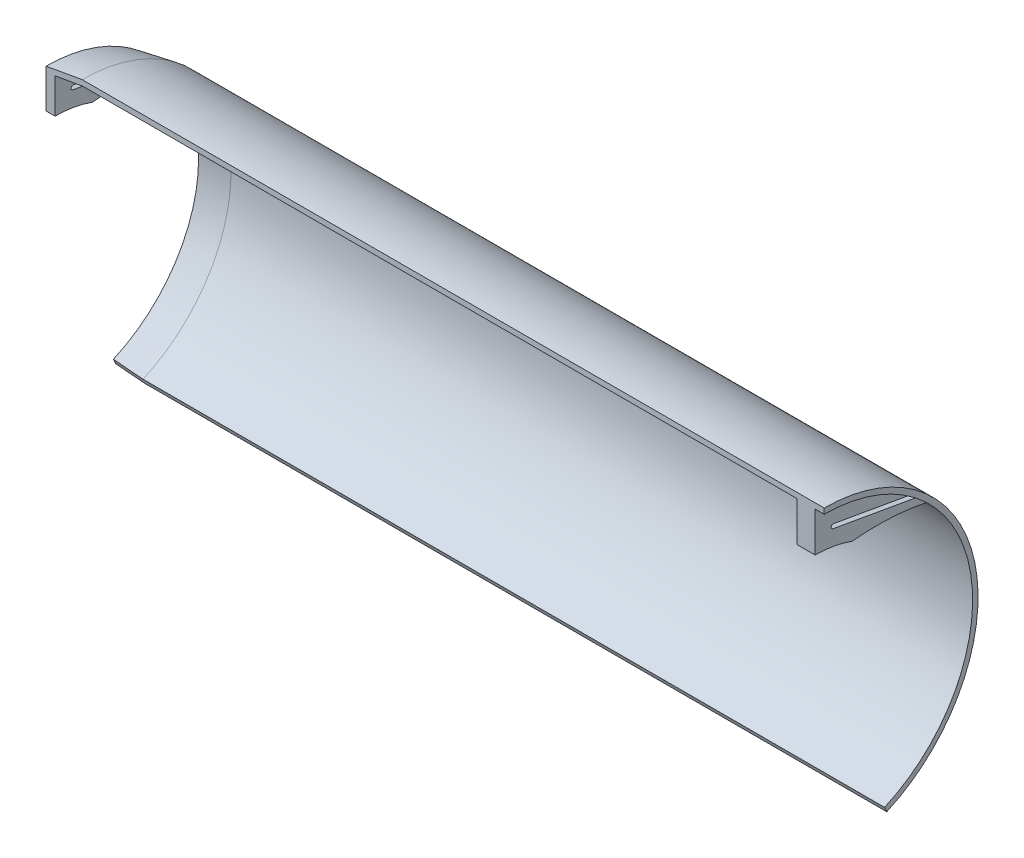
SolidWorks part; units mm, degrees
ref_plane "Front Plane" through (0, 0, 0) normal (0, 0, 1) x (1, 0, 0)
ref_plane "Top Plane" through (0, 0, 0) normal (0, 1, 0) x (1, 0, 0)
ref_plane "Right Plane" through (0, 0, 0) normal (1, 0, 0) x (0, 0, -1)
curve "Curve1"
  spline degree 3 poles (0, 0, 0) (-0.0123, 3.8916, 0) (-0.0274, 8.685, 0) (0.3616, 14.0857, 0) (0.5761, 16.0905, 0) (0.7825, 17.6048, 0) (0.9862, 18.8543, 0) (1.1887, 19.9315, 0) (1.3904, 20.8857, 0) (1.5917, 21.7465, 0) (1.7927, 22.5337, 0) (1.9935, 23.2611, 0) (2.1942, 23.9386, 0) (2.3947, 24.5739, 0) (2.5952, 25.1728, 0) (2.7956, 25.7401, 0) (2.9959, 26.2796, 0) (3.1962, 26.7943, 0) (3.3965, 27.2868, 0) (3.5967, 27.7594, 0) (3.7969, 28.2139, 0) (3.9971, 28.6519, 0) (4.1973, 29.0748, 0) (4.3974, 29.4838, 0) (4.5976, 29.8799, 0) (4.7977, 30.2641, 0) (4.9978, 30.6373, 0) (5.1979, 31.0001, 0) (5.398, 31.3533, 0) (5.5981, 31.6974, 0) (5.7982, 32.033, 0) (5.9983, 32.3606, 0) (6.1984, 32.6807, 0) (6.3985, 32.9935, 0) (6.5985, 33.2996, 0) (6.7986, 33.5993, 0) (6.9986, 33.8929, 0) (7.1987, 34.1806, 0) (7.3987, 34.4628, 0) (7.5988, 34.7397, 0) (7.7988, 35.0115, 0) (7.9989, 35.2785, 0) (8.1989, 35.5408, 0) (8.399, 35.7988, 0) (8.599, 36.0524, 0) (8.799, 36.3019, 0) (8.9991, 36.5476, 0) (9.1991, 36.7894, 0) (9.3991, 37.0275, 0) (9.5992, 37.2622, 0) (9.7992, 37.4934, 0) (9.9992, 37.7214, 0) (10.1992, 37.9461, 0) (10.3993, 38.1679, 0) (10.5993, 38.3866, 0) (10.7993, 38.6025, 0) (10.9993, 38.8156, 0) (11.1993, 39.026, 0) (11.3994, 39.2338, 0) (11.5994, 39.4391, 0) (11.7994, 39.6419, 0) (11.9994, 39.8422, 0) (12.1994, 40.0403, 0) (12.3995, 40.2361, 0) (12.5995, 40.4297, 0) (12.7995, 40.6212, 0) (12.9995, 40.8106, 0) (13.1995, 40.998, 0) (13.3995, 41.1834, 0) (13.5995, 41.3668, 0) (13.7995, 41.5484, 0) (13.9996, 41.7281, 0) (14.1996, 41.9061, 0) (14.3996, 42.0823, 0) (14.5996, 42.2568, 0) (14.7996, 42.4296, 0) (14.9996, 42.6008, 0) (15.1996, 42.7705, 0) (15.3996, 42.9385, 0) (15.5996, 43.1051, 0) (15.7996, 43.2701, 0) (15.9997, 43.4337, 0) (16.1997, 43.5959, 0) (16.3997, 43.7567, 0) (16.5997, 43.9161, 0) (16.7997, 44.0742, 0) (16.9997, 44.2309, 0) (17.1997, 44.3864, 0) (17.3997, 44.5406, 0) (17.5997, 44.6936, 0) (17.7997, 44.8453, 0) (17.9997, 44.9959, 0) (18.1997, 45.1453, 0) (18.3997, 45.2936, 0) (18.5997, 45.4407, 0) (18.7997, 45.5868, 0) (18.9997, 45.7317, 0) (19.1998, 45.8756, 0) (19.3998, 46.0185, 0) (19.5998, 46.1603, 0) (19.7998, 46.3011, 0) (19.9998, 46.4409, 0) (20.1998, 46.5797, 0) (20.3998, 46.7176, 0) (20.5998, 46.8546, 0) (20.7998, 46.9906, 0) (20.9998, 47.1257, 0) (21.1998, 47.2599, 0) (21.3998, 47.3932, 0) (21.5998, 47.5256, 0) (21.7998, 47.6572, 0) (21.9998, 47.788, 0) (22.1998, 47.9179, 0) (22.3998, 48.047, 0) (22.5998, 48.1753, 0) (22.7998, 48.3028, 0) (22.9998, 48.4295, 0) (23.1998, 48.5555, 0) (23.3998, 48.6807, 0) (23.5998, 48.8051, 0) (23.7998, 48.9288, 0) (23.9998, 49.0518, 0) (24.1998, 49.1741, 0) (24.3998, 49.2957, 0) (24.5998, 49.4165, 0) (24.7999, 49.5367, 0) (24.9999, 49.6562, 0) (25.1999, 49.7751, 0) (25.3999, 49.8933, 0) (25.5999, 50.0108, 0) (25.7999, 50.1277, 0) (25.9999, 50.2439, 0) (26.1999, 50.3596, 0) (26.3999, 50.4746, 0) (26.5999, 50.589, 0) (26.7999, 50.7028, 0) (26.9999, 50.8161, 0) (27.1999, 50.9287, 0) (27.3999, 51.0407, 0) (27.5999, 51.1522, 0) (27.7999, 51.2631, 0) (27.9999, 51.3735, 0) (28.1999, 51.4833, 0) (28.3999, 51.5926, 0) (28.5999, 51.7013, 0) (28.7999, 51.8095, 0) (28.9999, 51.9172, 0) (29.1999, 52.0243, 0) (29.3999, 52.131, 0) (29.5999, 52.2371, 0) (29.7999, 52.3428, 0) (29.9999, 52.4479, 0) (30.1999, 52.5526, 0) (30.3999, 52.6567, 0) (30.5999, 52.7604, 0) (30.7999, 52.8636, 0) (30.9999, 52.9664, 0) (31.1999, 53.0687, 0) (31.3999, 53.1705, 0) (31.5999, 53.2719, 0) (31.7999, 53.3728, 0) (31.9999, 53.4733, 0) (32.1999, 53.5733, 0) (32.3999, 53.6729, 0) (32.5999, 53.7721, 0) (32.7999, 53.8709, 0) (32.9999, 53.9692, 0) (33.1999, 54.0671, 0) (33.3999, 54.1646, 0) (33.5999, 54.2617, 0) (33.7999, 54.3584, 0) (33.9999, 54.4547, 0) (34.1999, 54.5506, 0) (34.3999, 54.6461, 0) (34.5999, 54.7412, 0) (34.7999, 54.836, 0) (34.9999, 54.9303, 0) (35.1999, 55.0243, 0) (35.3999, 55.1179, 0) (35.5999, 55.2111, 0) (35.7999, 55.304, 0) (35.9999, 55.3965, 0) (36.1999, 55.4887, 0) (36.3999, 55.5805, 0) (36.5999, 55.6719, 0) (36.7999, 55.763, 0) (36.9999, 55.8537, 0) (37.1999, 55.9441, 0) (37.3999, 56.0342, 0) (37.5999, 56.1239, 0) (37.7999, 56.2133, 0) (37.9999, 56.3024, 0) (38.1999, 56.3911, 0) (38.3999, 56.4795, 0) (38.5999, 56.5676, 0) (38.7999, 56.6554, 0) (38.9999, 56.7428, 0) (39.1999, 56.83, 0) (39.3999, 56.9168, 0) (39.5999, 57.0033, 0) (39.7999, 57.0896, 0) (39.9999, 57.1755, 0) (40.1999, 57.2611, 0) (40.3999, 57.3464, 0) (40.5999, 57.4314, 0) (40.7999, 57.5161, 0) (40.9999, 57.6006, 0) (41.1999, 57.6847, 0) (41.3999, 57.7686, 0) (41.6, 57.8522, 0) (41.8, 57.9355, 0) (42, 58.0185, 0) (42.2, 58.1012, 0) (42.4, 58.1837, 0) (42.6, 58.2659, 0) (42.8, 58.3479, 0) (43, 58.4295, 0) (43.2, 58.5109, 0) (43.4, 58.592, 0) (43.6, 58.6729, 0) (43.8, 58.7535, 0) (44, 58.8339, 0) (44.2, 58.914, 0) (44.4, 58.9938, 0) (44.6, 59.0734, 0) (44.8, 59.1528, 0) (45, 59.2319, 0) (45.2, 59.3107, 0) (45.4, 59.3893, 0) (45.6, 59.4677, 0) (45.8, 59.5458, 0) (46, 59.6237, 0) (46.2, 59.7014, 0) (46.4, 59.7788, 0) (46.6, 59.856, 0) (46.8, 59.9329, 0) (47, 60.0096, 0) (47.2, 60.0861, 0) (47.4, 60.1624, 0) (47.6, 60.2385, 0) (47.8, 60.3143, 0) (48, 60.3899, 0) (48.2, 60.4652, 0) (48.4, 60.5404, 0) (48.6, 60.6153, 0) (48.8, 60.6901, 0) (49, 60.7646, 0) (49.2, 60.8389, 0) (49.4, 60.913, 0) (49.6, 60.9869, 0) (49.8, 61.0605, 0) (50, 61.134, 0) (50.2, 61.2072, 0) (50.4, 61.2803, 0) (50.6, 61.3531, 0) (50.8, 61.4258, 0) (51, 61.4982, 0) (51.2, 61.5705, 0) (51.4, 61.6426, 0) (51.6, 61.7144, 0) (51.8, 61.7861, 0) (52, 61.8575, 0) (52.2, 61.9288, 0) (52.4, 61.9999, 0) (52.6, 62.0708, 0) (52.8, 62.1415, 0) (53, 62.212, 0) (53.2, 62.2824, 0) (53.4, 62.3525, 0) (53.6, 62.4225, 0) (53.8, 62.4923, 0) (54, 62.5619, 0) (54.2, 62.6313, 0) (54.4, 62.7006, 0) (54.6, 62.7696, 0) (54.8, 62.8385, 0) (55, 62.9072, 0) (55.2, 62.9758, 0) (55.4, 63.0441, 0) (55.6, 63.1123, 0) (55.8, 63.1803, 0) (56, 63.2482, 0) (56.2, 63.3159, 0) (56.4, 63.3834, 0) (56.6, 63.4507, 0) (56.8, 63.5179, 0) (57, 63.5849, 0) (57.2, 63.6518, 0) (57.4, 63.7185, 0) (57.6, 63.785, 0) (57.8, 63.8513, 0) (58, 63.9175, 0) (58.2, 63.9836, 0) (58.4, 64.0495, 0) (58.6, 64.1152, 0) (58.8, 64.1808, 0) (59, 64.2462, 0) (59.2, 64.3114, 0) (59.4, 64.3765, 0) (59.6, 64.4415, 0) (59.8, 64.5063, 0) (60, 64.5709, 0) (60.2, 64.6354, 0) (60.4, 64.6998, 0) (60.6, 64.764, 0) (60.8, 64.828, 0) (61, 64.8919, 0) (61.2, 64.9557, 0) (61.4, 65.0193, 0) (61.6, 65.0827, 0) (61.8, 65.1461, 0) (62, 65.2092, 0) (62.2, 65.2723, 0) (62.4, 65.3352, 0) (62.6, 65.3979, 0) (62.8, 65.4605, 0) (63, 65.523, 0) (63.2, 65.5853, 0) (63.4, 65.6475, 0) (63.6, 65.7096, 0) (63.8, 65.7715, 0) (64, 65.8333, 0) (64.2, 65.895, 0) (64.4, 65.9565, 0) (64.6, 66.0179, 0) (64.8, 66.0791, 0) (65, 66.1402, 0) (65.2, 66.2012, 0) (65.4, 66.2621, 0) (65.6, 66.3228, 0) (65.8, 66.3834, 0) (66, 66.4439, 0) (66.2, 66.5042, 0) (66.4, 66.5644, 0) (66.6, 66.6245, 0) (66.8, 66.6845, 0) (67, 66.7443, 0) (67.2, 66.804, 0) (67.4, 66.8636, 0) (67.6, 66.923, 0) (67.8, 66.9824, 0) (68, 67.0416, 0) (68.2, 67.1007, 0) (68.4, 67.1597, 0) (68.6, 67.2185, 0) (68.8, 67.2772, 0) (69, 67.3359, 0) (69.2, 67.3943, 0) (69.4, 67.4527, 0) (69.6, 67.511, 0) (69.8, 67.5691, 0) (70, 67.6271, 0) (70.2, 67.6851, 0) (70.4, 67.7428, 0) (70.6, 67.8005, 0) (70.8, 67.8581, 0) (71, 67.9155, 0) (71.2, 67.9729, 0) (71.4, 68.0301, 0) (71.6, 68.0872, 0) (71.8, 68.1442, 0) (72, 68.2011, 0) (72.2, 68.2579, 0) (72.4, 68.3145, 0) (72.6, 68.3711, 0) (72.8, 68.4276, 0) (73, 68.4839, 0) (73.2, 68.5401, 0) (73.4, 68.5963, 0) (73.6, 68.6523, 0) (73.8, 68.7082, 0) (74, 68.764, 0) (74.2, 68.8197, 0) (74.4, 68.8753, 0) (74.6, 68.9308, 0) (74.8, 68.9862, 0) (75, 69.0415, 0) (75.2, 69.0966, 0) (75.4, 69.1517, 0) (75.6, 69.2067, 0) (75.8, 69.2616, 0) (76, 69.3164, 0) (76.2, 69.371, 0) (76.4, 69.4256, 0) (76.6, 69.4801, 0) (76.8, 69.5344, 0) (77, 69.5887, 0) (77.2, 69.6429, 0) (77.4, 69.697, 0) (77.6, 69.751, 0) (77.8, 69.8048, 0) (78, 69.8586, 0) (78.2, 69.9123, 0) (78.4, 69.9659, 0) (78.6, 70.0194, 0) (78.8, 70.0728, 0) (79, 70.1261, 0) (79.2, 70.1793, 0) (79.4, 70.2324, 0) (79.6, 70.2855, 0) (79.8, 70.3384, 0) (80, 70.3912, 0) (80.2, 70.444, 0) (80.4, 70.4966, 0) (80.6, 70.5492, 0) (80.8, 70.6017, 0) (81, 70.6541, 0) (81.2, 70.7064, 0) (81.4, 70.7586, 0) (81.6, 70.8107, 0) (81.8, 70.8627, 0) (82, 70.9146, 0) (82.2, 70.9665, 0) (82.4, 71.0182, 0) (82.6, 71.0699, 0) (82.8, 71.1215, 0) (83, 71.173, 0) (83.2, 71.2244, 0) (83.4, 71.2757, 0) (83.6, 71.3269, 0) (83.8, 71.3781, 0) (84, 71.4291, 0) (84.2, 71.4801, 0) (84.4, 71.531, 0) (84.6, 71.5818, 0) (84.8, 71.6325, 0) (85, 71.6832, 0) (85.2, 71.7337, 0) (85.4, 71.7842, 0) (85.6, 71.8346, 0) (85.8, 71.8849, 0) (86, 71.9351, 0) (86.2, 71.9853, 0) (86.4, 72.0354, 0) (86.6, 72.0853, 0) (86.8, 72.1352, 0) (87, 72.1851, 0) (87.2, 72.2348, 0) (87.4, 72.2845, 0) (87.6, 72.3341, 0) (87.8, 72.3836, 0) (88, 72.433, 0) (88.2, 72.4823, 0) (88.4, 72.5316, 0) (88.6, 72.5808, 0) (88.8, 72.6299, 0) (89, 72.6789, 0) (89.2, 72.7279, 0) (89.4, 72.7768, 0) (89.6, 72.8256, 0) (89.8, 72.8743, 0) (90, 72.923, 0) (90.2, 72.9716, 0) (90.4, 73.0201, 0) (90.6, 73.0685, 0) (90.8, 73.1168, 0) (91, 73.1651, 0) (91.2, 73.2133, 0) (91.4, 73.2614, 0) (91.6, 73.3095, 0) (91.8, 73.3575, 0) (92, 73.4054, 0) (92.2, 73.4532, 0) (92.4, 73.501, 0) (92.6, 73.5487, 0) (92.8, 73.5963, 0) (93, 73.6439, 0) (93.2, 73.6913, 0) (93.4, 73.7387, 0) (93.6, 73.7861, 0) (93.8, 73.8333, 0) (94, 73.8805, 0) (94.2, 73.9276, 0) (94.4, 73.9747, 0) (94.6, 74.0217, 0) (94.8, 74.0686, 0) (95, 74.1154, 0) (95.2, 74.1622, 0) (95.4, 74.2089, 0) (95.6, 74.2556, 0) (95.8, 74.3021, 0) (96, 74.3486, 0) (96.2, 74.3951, 0) (96.4, 74.4414, 0) (96.6, 74.4877, 0) (96.8, 74.534, 0) (97, 74.5801, 0) (97.2, 74.6262, 0) (97.4, 74.6723, 0) (97.6, 74.7182, 0) (97.8, 74.7641, 0) (98, 74.81, 0) (98.2, 74.8557, 0) (98.4, 74.9014, 0) (98.6, 74.9471, 0) (98.8, 74.9926, 0) (99, 75.0382, 0) (99.2, 75.0836, 0) (99.4, 75.129, 0) (99.6, 75.1743, 0) (99.8, 75.2196, 0) (100, 75.2647, 0) (100.2, 75.3099, 0) (100.4, 75.3549, 0) (100.6, 75.3999, 0) (100.8, 75.4449, 0) (101, 75.4898, 0) (101.2, 75.5346, 0) (101.4, 75.5793, 0) (101.6, 75.624, 0) (101.8, 75.6686, 0) (102, 75.7132, 0) (102.2, 75.7577, 0) (102.4, 75.8022, 0) (102.6, 75.8465, 0) (102.8, 75.8909, 0) (103, 75.9351, 0) (103.2, 75.9793, 0) (103.4, 76.0235, 0) (103.6, 76.0676, 0) (103.8, 76.1116, 0) (104, 76.1556, 0) (104.2, 76.1995, 0) (104.4, 76.2433, 0) (104.6, 76.2871, 0) (104.8, 76.3308, 0) (105, 76.3745, 0) (105.2, 76.4181, 0) (105.4, 76.4617, 0) (105.6, 76.5052, 0) (105.8, 76.5486, 0) (106, 76.592, 0) (106.2, 76.6353, 0) (106.4, 76.6786, 0) (106.6, 76.7218, 0) (106.8, 76.7649, 0) (107, 76.808, 0) (107.2, 76.8511, 0) (107.4, 76.8941, 0) (107.6, 76.937, 0) (107.8, 76.9799, 0) (108, 77.0227, 0) (108.2, 77.0655, 0) (108.4, 77.1082, 0) (108.6, 77.1508, 0) (108.8, 77.1934, 0) (109, 77.236, 0) (109.2, 77.2784, 0) (109.4, 77.3209, 0) (109.6, 77.3633, 0) (109.8, 77.4056, 0) (110, 77.4479, 0) (110.2, 77.4901, 0) (110.4, 77.5322, 0) (110.6, 77.5743, 0) (110.8, 77.6164, 0) (111, 77.6584, 0) (111.2, 77.7004, 0) (111.4, 77.7423, 0) (111.6, 77.7841, 0) (111.8, 77.8259, 0) (112, 77.8676, 0) (112.2, 77.9093, 0) (112.4, 77.951, 0) (112.6, 77.9925, 0) (112.8, 78.0341, 0) (113, 78.0756, 0) (113.2, 78.117, 0) (113.4, 78.1584, 0) (113.6, 78.1997, 0) (113.8, 78.241, 0) (114, 78.2822, 0) (114.2, 78.3234, 0) (114.4, 78.3645, 0) (114.6, 78.4056, 0) (114.8, 78.4466, 0) (115, 78.4876, 0) (115.2, 78.5285, 0) (115.4, 78.5694, 0) (115.6, 78.6102, 0) (115.8, 78.651, 0) (116, 78.6917, 0) (116.2, 78.7324, 0) (116.4, 78.773, 0) (116.6, 78.8136, 0) (116.8, 78.8541, 0) (117, 78.8946, 0) (117.2, 78.935, 0) (117.4, 78.9754, 0) (117.6, 79.0158, 0) (117.8, 79.0561, 0) (118, 79.0963, 0) (118.2, 79.1365, 0) (118.4, 79.1766, 0) (118.6, 79.2167, 0) (118.8, 79.2568, 0) (119, 79.2968, 0) (119.2, 79.3368, 0) (119.4, 79.3767, 0) (119.6, 79.4165, 0) (119.8, 79.4564, 0) (120, 79.4961, 0) (120.2, 79.5358, 0) (120.4, 79.5755, 0) (120.6, 79.6152, 0) (120.8, 79.6547, 0) (121, 79.6943, 0) (121.2, 79.7338, 0) (121.4, 79.7732, 0) (121.6, 79.8126, 0) (121.8, 79.852, 0) (122, 79.8913, 0) (122.2, 79.9306, 0) (122.4, 79.9698, 0) (122.6, 80.009, 0) (122.8, 80.0481, 0) (123, 80.0872, 0) (123.2, 80.1262, 0) (123.4, 80.1652, 0) (123.6, 80.2042, 0) (123.8, 80.2431, 0) (124, 80.282, 0) (124.2, 80.3208, 0) (124.4, 80.3596, 0) (124.6, 80.3983, 0) (124.8, 80.437, 0) (125, 80.4757, 0) (125.2, 80.5143, 0) (125.4, 80.5528, 0) (125.6, 80.5914, 0) (125.8, 80.6298, 0) (126, 80.6683, 0) (126.2, 80.7067, 0) (126.4, 80.745, 0) (126.6, 80.7833, 0) (126.8, 80.8216, 0) (127, 80.8598, 0) (127.2, 80.898, 0) (127.4, 80.9361, 0) (127.6, 80.9742, 0) (127.8, 81.0123, 0) (128, 81.0503, 0) (128.2, 81.0883, 0) (128.4, 81.1262, 0) (128.6, 81.1641, 0) (128.8, 81.2019, 0) (129, 81.2397, 0) (129.2, 81.2775, 0) (129.4, 81.3152, 0) (129.6, 81.3529, 0) (129.8, 81.3906, 0) (130, 81.4282, 0) (130.2, 81.4657, 0) (130.4, 81.5032, 0) (130.6, 81.5407, 0) (130.8, 81.5782, 0) (131, 81.6156, 0) (131.2, 81.6529, 0) (131.4, 81.6902, 0) (131.6, 81.7275, 0) (131.8, 81.7648, 0) (132, 81.802, 0) (132.2, 81.8391, 0) (132.4, 81.8763, 0) (132.6, 81.9133, 0) (132.8, 81.9504, 0) (133, 81.9874, 0) (133.2, 82.0244, 0) (133.4, 82.0613, 0) (133.6, 82.0982, 0) (133.8, 82.135, 0) (134, 82.1718, 0) (134.2, 82.2086, 0) (134.4, 82.2454, 0) (134.6, 82.282, 0) (134.8, 82.3187, 0) (135, 82.3553, 0) (135.2, 82.3919, 0) (135.4, 82.4285, 0) (135.6, 82.465, 0) (135.8, 82.5014, 0) (136, 82.5379, 0) (136.2, 82.5743, 0) (136.4, 82.6106, 0) (136.6, 82.6469, 0) (136.8, 82.6832, 0) (137, 82.7195, 0) (137.2, 82.7557, 0) (137.4, 82.7919, 0) (137.6, 82.828, 0) (137.8, 82.8641, 0) (138, 82.9001, 0) (138.2, 82.9362, 0) (138.4, 82.9722, 0) (138.6, 83.0081, 0) (138.8, 83.044, 0) (139, 83.0799, 0) (139.2, 83.1158, 0) (139.4, 83.1516, 0) (139.6, 83.1873, 0) (139.8, 83.2231, 0) (140, 83.2588, 0) (140.2, 83.2944, 0) (140.4, 83.3301, 0) (140.6, 83.3657, 0) (140.8, 83.4012, 0) (141, 83.4367, 0) (141.2, 83.4722, 0) (141.4, 83.5077, 0) (141.6, 83.5431, 0) (141.8, 83.5785, 0) (142, 83.6138, 0) (142.2, 83.6491, 0) (142.4, 83.6844, 0) (142.6, 83.7197, 0) (142.8, 83.7549, 0) (143, 83.79, 0) (143.2, 83.8252, 0) (143.4, 83.8603, 0) (143.6, 83.8954, 0) (143.8, 83.9304, 0) (144, 83.9654, 0) (144.2, 84.0004, 0) (144.4, 84.0353, 0) (144.6, 84.0702, 0) (144.8, 84.1051, 0) (145, 84.1399, 0) (145.2, 84.1747, 0) (145.4, 84.2095, 0) (145.6, 84.2442, 0) (145.8, 84.2789, 0) (146, 84.3136, 0) (146.2, 84.3482, 0) (146.4, 84.3828, 0) (146.6, 84.4174, 0) (146.8, 84.4519, 0) (147, 84.4864, 0) (147.2, 84.5209, 0) (147.4, 84.5553, 0) (147.6, 84.5897, 0) (147.8, 84.6241, 0) (148, 84.6584, 0) (148.2, 84.6927, 0) (148.4, 84.727, 0) (148.6, 84.7612, 0) (148.8, 84.7954, 0) (149, 84.8296, 0) (149.2, 84.8638, 0) (149.4, 84.8979, 0) (149.6, 84.9319, 0) (149.8, 84.966, 0) (149.9333, 84.9887, 0) (150, 85, 0) knots 0 0 0 0 0.061462 0.075706 0.085548 0.093322 0.099856 0.105554 0.110643 0.115268 0.119525 0.123482 0.127192 0.130691 0.13401 0.137173 0.140199 0.143104 0.145901 0.148602 0.151215 0.15375 0.156213 0.158609 0.160946 0.163227 0.165456 0.167638 0.169775 0.171871 0.173928 0.17595 0.177937 0.179893 0.181819 0.183716 0.185587 0.187433 0.189255 0.191054 0.192831 0.194589 0.196326 0.198045 0.199747 0.201431 0.2031 0.204753 0.206391 0.208015 0.209626 0.211223 0.212808 0.214381 0.215942 0.217493 0.219032 0.220561 0.22208 0.22359 0.225091 0.226582 0.228065 0.229539 0.231006 0.232464 0.233915 0.235359 0.236795 0.238225 0.239648 0.241065 0.242475 0.243879 0.245277 0.24667 0.248057 0.249438 0.250814 0.252185 0.253551 0.254913 0.256269 0.257621 0.258968 0.260311 0.26165 0.262984 0.264315 0.265641 0.266964 0.268282 0.269598 0.270909 0.272217 0.273522 0.274823 0.276121 0.277416 0.278707 0.279996 0.281281 0.282564 0.283843 0.28512 0.286394 0.287666 0.288935 0.290201 0.291465 0.292726 0.293985 0.295241 0.296495 0.297747 0.298996 0.300243 0.301489 0.302732 0.303972 0.305211 0.306448 0.307683 0.308916 0.310147 0.311376 0.312604 0.313829 0.315053 0.316275 0.317495 0.318714 0.319931 0.321147 0.32236 0.323573 0.324783 0.325993 0.3272 0.328406 0.329611 0.330815 0.332017 0.333217 0.334416 0.335614 0.336811 0.338006 0.3392 0.340393 0.341584 0.342775 0.343964 0.345152 0.346339 0.347524 0.348709 0.349892 0.351074 0.352256 0.353436 0.354615 0.355793 0.35697 0.358146 0.359321 0.360495 0.361668 0.36284 0.364011 0.365182 0.366351 0.36752 0.368687 0.369854 0.37102 0.372185 0.373349 0.374512 0.375674 0.376836 0.377997 0.379157 0.380316 0.381475 0.382632 0.383789 0.384946 0.386101 0.387256 0.38841 0.389563 0.390716 0.391868 0.393019 0.39417 0.39532 0.396469 0.397618 0.398766 0.399913 0.40106 0.402206 0.403351 0.404496 0.40564 0.406784 0.407927 0.409069 0.410211 0.411353 0.412493 0.413633 0.414773 0.415912 0.417051 0.418189 0.419326 0.420463 0.4216 0.422736 0.423871 0.425006 0.426141 0.427275 0.428408 0.429541 0.430674 0.431806 0.432937 0.434068 0.435199 0.436329 0.437459 0.438588 0.439717 0.440846 0.441974 0.443101 0.444229 0.445355 0.446482 0.447608 0.448733 0.449858 0.450983 0.452107 0.453231 0.454355 0.455478 0.456601 0.457723 0.458845 0.459967 0.461088 0.462209 0.46333 0.46445 0.46557 0.46669 0.467809 0.468928 0.470046 0.471164 0.472282 0.4734 0.474517 0.475634 0.47675 0.477866 0.478982 0.480098 0.481213 0.482328 0.483443 0.484557 0.485671 0.486785 0.487898 0.489011 0.490124 0.491237 0.492349 0.493461 0.494573 0.495684 0.496796 0.497906 0.499017 0.500127 0.501237 0.502347 0.503457 0.504566 0.505675 0.506784 0.507892 0.509001 0.510109 0.511216 0.512324 0.513431 0.514538 0.515645 0.516752 0.517858 0.518964 0.52007 0.521175 0.522281 0.523386 0.524491 0.525595 0.5267 0.527804 0.528908 0.530012 0.531116 0.532219 0.533322 0.534425 0.535528 0.53663 0.537733 0.538835 0.539937 0.541038 0.54214 0.543241 0.544342 0.545443 0.546544 0.547644 0.548745 0.549845 0.550945 0.552044 0.553144 0.554243 0.555342 0.556441 0.55754 0.558639 0.559737 0.560836 0.561934 0.563032 0.564129 0.565227 0.566324 0.567421 0.568518 0.569615 0.570712 0.571809 0.572905 0.574001 0.575097 0.576193 0.577289 0.578384 0.57948 0.580575 0.58167 0.582765 0.58386 0.584954 0.586049 0.587143 0.588237 0.589331 0.590425 0.591519 0.592612 0.593706 0.594799 0.595892 0.596985 0.598078 0.59917 0.600263 0.601355 0.602448 0.60354 0.604632 0.605724 0.606815 0.607907 0.608998 0.61009 0.611181 0.612272 0.613363 0.614453 0.615544 0.616635 0.617725 0.618815 0.619905 0.620995 0.622085 0.623175 0.624265 0.625354 0.626443 0.627533 0.628622 0.629711 0.6308 0.631888 0.632977 0.634066 0.635154 0.636242 0.637331 0.638419 0.639507 0.640594 0.641682 0.64277 0.643857 0.644945 0.646032 0.647119 0.648206 0.649293 0.65038 0.651467 0.652553 0.65364 0.654726 0.655813 0.656899 0.657985 0.659071 0.660157 0.661243 0.662328 0.663414 0.664499 0.665585 0.66667 0.667755 0.66884 0.669925 0.67101 0.672095 0.67318 0.674264 0.675349 0.676433 0.677518 0.678602 0.679686 0.68077 0.681854 0.682938 0.684022 0.685105 0.686189 0.687272 0.688356 0.689439 0.690522 0.691605 0.692688 0.693771 0.694854 0.695937 0.69702 0.698102 0.699185 0.700267 0.70135 0.702432 0.703514 0.704596 0.705678 0.70676 0.707842 0.708924 0.710006 0.711087 0.712169 0.71325 0.714332 0.715413 0.716494 0.717575 0.718656 0.719737 0.720818 0.721899 0.72298 0.724061 0.725141 0.726222 0.727302 0.728382 0.729463 0.730543 0.731623 0.732703 0.733783 0.734863 0.735943 0.737023 0.738103 0.739182 0.740262 0.741341 0.742421 0.7435 0.744579 0.745659 0.746738 0.747817 0.748896 0.749975 0.751054 0.752133 0.753211 0.75429 0.755369 0.756447 0.757526 0.758604 0.759682 0.760761 0.761839 0.762917 0.763995 0.765073 0.766151 0.767229 0.768307 0.769385 0.770462 0.77154 0.772618 0.773695 0.774773 0.77585 0.776927 0.778005 0.779082 0.780159 0.781236 0.782313 0.78339 0.784467 0.785544 0.786621 0.787698 0.788774 0.789851 0.790928 0.792004 0.793081 0.794157 0.795233 0.79631 0.797386 0.798462 0.799538 0.800614 0.80169 0.802766 0.803842 0.804918 0.805994 0.80707 0.808145 0.809221 0.810296 0.811372 0.812447 0.813523 0.814598 0.815674 0.816749 0.817824 0.818899 0.819974 0.821049 0.822124 0.823199 0.824274 0.825349 0.826424 0.827499 0.828573 0.829648 0.830723 0.831797 0.832872 0.833946 0.835021 0.836095 0.837169 0.838244 0.839318 0.840392 0.841466 0.84254 0.843614 0.844688 0.845762 0.846836 0.84791 0.848984 0.850058 0.851131 0.852205 0.853279 0.854352 0.855426 0.856499 0.857573 0.858646 0.859719 0.860793 0.861866 0.862939 0.864012 0.865085 0.866159 0.867232 0.868305 0.869378 0.87045 0.871523 0.872596 0.873669 0.874742 0.875814 0.876887 0.87796 0.879032 0.880105 0.881177 0.88225 0.883322 0.884395 0.885467 0.886539 0.887611 0.888684 0.889756 0.890828 0.8919 0.892972 0.894044 0.895116 0.896188 0.89726 0.898332 0.899404 0.900475 0.901547 0.902619 0.90369 0.904762 0.905834 0.906905 0.907977 0.909048 0.91012 0.911191 0.912262 0.913334 0.914405 0.915476 0.916548 0.917619 0.91869 0.919761 0.920832 0.921903 0.922974 0.924045 0.925116 0.926187 0.927258 0.928329 0.929399 0.93047 0.931541 0.932612 0.933682 0.934753 0.935823 0.936894 0.937965 0.939035 0.940105 0.941176 0.942246 0.943317 0.944387 0.945457 0.946527 0.947598 0.948668 0.949738 0.950808 0.951878 0.952948 0.954018 0.955088 0.956158 0.957228 0.958298 0.959368 0.960438 0.961508 0.962577 0.963647 0.964717 0.965786 0.966856 0.967926 0.968995 0.970065 0.971134 0.972204 0.973273 0.974343 0.975412 0.976481 0.977551 0.97862 0.979689 0.980759 0.981828 0.982897 0.983966 0.985035 0.986104 0.987173 0.988242 0.989311 0.99038 0.991449 0.992518 0.993587 0.994656 0.995725 0.996794 0.997863 0.998931 1 1 1 1
sketch "Sketch1" plane through (0, 0, 0) normal (0, 0, 1) x (1, 0, 0)
  line L0 (150, 85) -> (560, 85)
  line L1 (150.2533, 82) -> (560, 82)
  line L2 (560, 85) -> (560, 82)
  line L3 (0, 0) -> (3, 0)
  line L4 (3, 0.0095) -> (3, 0)
  line L5 (3, 0) -> (560, 0) construction
  line L6 (560, 0) -> (560, 82) construction
  line L8 (140, -75) -> (540, -75) construction
  line L9 (130, 78.3755) -> (135, 78.3755)
  line L10 (140, -75) -> (140, 75) construction
  line L11 (140, 75) -> (540, 75) construction
  line L12 (135, 79.3054) -> (135, 60)
  line L13 (135, 60) -> (130, 60)
  line L14 (130, 60) -> (130, 81.4281)
  line L15 (555, 60) -> (555, 82)
  line L16 (545, 82) -> (545, 60)
  line L17 (545, 60) -> (555, 60)
  line L18 (540, -75) -> (540, 75) construction
  line L19 (140, -75) -> (540, 75) construction
  line L20 (140, 75) -> (540, -75) construction
  spline S0 degree 3 poles (-1988.6566, -159.7184) (98.3599, -158.1291) (-5.7084, -70.1856) (0.3616, 14.0857) (0.5761, 16.0905) (0.7825, 17.6048) (0.9862, 18.8543) (1.1887, 19.9315) (1.3904, 20.8857) (1.5917, 21.7465) (1.7927, 22.5337) (1.9935, 23.2611) (2.2538, 24.14) (2.5806, 25.1462) (2.9836, 26.2595) (3.3859, 27.2713) (3.7877, 28.2016) (4.1891, 29.0648) (4.5903, 29.8717) (5.0533, 30.7478) (5.5832, 31.6835) (6.1854, 32.6697) (6.7872, 33.5906) (7.4515, 34.5461) (8.1828, 35.531) (8.9851, 36.54) (9.8503, 37.5625) (10.7826, 38.5957) (11.785, 39.6369) (12.851, 40.6804) (13.984, 41.7246) (15.1862, 42.7682) (16.388, 43.7553) (17.6544, 44.7435) (18.9876, 45.7315) (20.3892, 46.7179) (21.7905, 47.6579) (23.2571, 48.5984) (24.7904, 49.5382) (26.3916, 50.4762) (28.0583, 51.4122) (29.7917, 52.3451) (31.5927, 53.2742) (33.4594, 54.1996) (35.3929, 55.1207) (37.4597, 56.0672) (39.5933, 57.0066) (41.8602, 57.9666) (44.1937, 58.9175) (46.6606, 59.8853) (49.2604, 60.8677) (51.994, 61.8617) (54.861, 62.8656) (57.7946, 63.8556) (60.8615, 64.8536) (64.0615, 65.8584) (67.4615, 66.8882) (70.9951, 67.9202) (74.6621, 68.9539) (78.4621, 69.9886) (82.4622, 71.0404) (86.6623, 72.1071) (91.0624, 73.1864) (95.6625, 74.2764) (100.4626, 75.3753) (105.4628, 76.4816) (110.6629, 77.5938) (116.063, 78.7107) (121.6632, 79.8312) (127.5299, 80.9671) (133.6633, 82.1162) (140.0634, 83.2764) (145.1985, 84.1774) (148.3332, 84.7158) (149.3333, 84.8865) (149.6, 84.9319) (194.4783, 92.5723) (239.7917, 97.2513) (-50.3187, 2073.1568) knots -1.249314 -1.249314 -1.249314 -1.249314 0.061462 0.075706 0.085548 0.093322 0.099856 0.105554 0.110643 0.115268 0.119525 0.123482 0.127192 0.13401 0.140199 0.145901 0.151215 0.156213 0.160946 0.165456 0.171871 0.177937 0.183716 0.189255 0.196326 0.2031 0.209626 0.217493 0.225091 0.232464 0.241065 0.249438 0.257621 0.265641 0.274823 0.283843 0.292726 0.301489 0.311376 0.321147 0.330815 0.341584 0.352256 0.36284 0.374512 0.386101 0.398766 0.411353 0.425006 0.438588 0.453231 0.468928 0.484557 0.501237 0.517858 0.535528 0.554243 0.574001 0.593706 0.614453 0.636242 0.659071 0.682938 0.707842 0.733783 0.760761 0.788774 0.817824 0.84791 0.879032 0.912262 0.946527 0.981828 0.994656 0.996794 0.997863 0.998931 1.716252 1.716252 1.716252 1.716252 only from (0, 0) to (150, 85) construction
  spline S1 degree 3 poles (0, 0) (-0.0123, 3.8916) (-0.0274, 8.685) (0.3616, 14.0857) (0.5761, 16.0905) (0.7825, 17.6048) (0.9862, 18.8543) (1.1887, 19.9315) (1.3904, 20.8857) (1.5917, 21.7465) (1.7927, 22.5337) (1.9935, 23.2611) (2.2538, 24.14) (2.5806, 25.1462) (2.9836, 26.2595) (3.3859, 27.2713) (3.7877, 28.2016) (4.1891, 29.0648) (4.5903, 29.8717) (5.0533, 30.7478) (5.5832, 31.6835) (6.1854, 32.6697) (6.7872, 33.5906) (7.4515, 34.5461) (8.1828, 35.531) (8.9851, 36.54) (9.8503, 37.5625) (10.7826, 38.5957) (11.785, 39.6369) (12.851, 40.6804) (13.984, 41.7246) (15.1862, 42.7682) (16.388, 43.7553) (17.6544, 44.7435) (18.9876, 45.7315) (20.3892, 46.7179) (21.7905, 47.6579) (23.2571, 48.5984) (24.7904, 49.5382) (26.3916, 50.4762) (28.0583, 51.4122) (29.7917, 52.3451) (31.5927, 53.2742) (33.4594, 54.1996) (35.3929, 55.1207) (37.4597, 56.0672) (39.5933, 57.0066) (41.8602, 57.9666) (44.1937, 58.9175) (46.6606, 59.8853) (49.2604, 60.8677) (51.994, 61.8617) (54.861, 62.8656) (57.7946, 63.8556) (60.8615, 64.8536) (64.0615, 65.8584) (67.4615, 66.8882) (70.9951, 67.9202) (74.6621, 68.9539) (78.4621, 69.9886) (82.4622, 71.0404) (86.6623, 72.1071) (91.0624, 73.1864) (95.6625, 74.2764) (100.4626, 75.3753) (105.4628, 76.4816) (110.6629, 77.5938) (116.063, 78.7107) (121.6632, 79.8312) (127.5299, 80.9671) (133.6633, 82.1162) (140.0634, 83.2764) (145.1985, 84.1774) (148.3332, 84.7158) (149.4, 84.8979) (149.7333, 84.9547) (149.9333, 84.9887) (150, 85) knots 0 0 0 0 0.061462 0.075706 0.085548 0.093322 0.099856 0.105554 0.110643 0.115268 0.119525 0.123482 0.127192 0.13401 0.140199 0.145901 0.151215 0.156213 0.160946 0.165456 0.171871 0.177937 0.183716 0.189255 0.196326 0.2031 0.209626 0.217493 0.225091 0.232464 0.241065 0.249438 0.257621 0.265641 0.274823 0.283843 0.292726 0.301489 0.311376 0.321147 0.330815 0.341584 0.352256 0.36284 0.374512 0.386101 0.398766 0.411353 0.425006 0.438588 0.453231 0.468928 0.484557 0.501237 0.517858 0.535528 0.554243 0.574001 0.593706 0.614453 0.636242 0.659071 0.682938 0.707842 0.733783 0.760761 0.788774 0.817824 0.84791 0.879032 0.912262 0.946527 0.981828 0.994656 0.996794 0.998931 1 1 1 1
  spline S4 degree 1 poles (3, 0.0095) (150.2533, 82) knots 0 0 1 1 construction
  spline S5 degree 3 poles (3, 0.0095) (2.9938, 1.9694) (2.982, 5.9112) (3.1447, 11.6915) (3.6709, 17.3262) (4.8192, 22.7297) (6.752, 27.816) (10.434, 34.0689) (16.886, 40.7698) (26.3115, 47.2193) (36.5885, 52.5329) (47.3393, 57.0416) (62.0527, 62.2707) (80.8898, 67.7174) (103.8331, 73.1782) (119.8433, 76.4414) (128.9979, 78.1869) (130.8328, 78.5327) (132.4993, 78.8436) (134.1662, 79.1526) (140.0771, 80.2373) (145.5819, 81.205) (150.2533, 82) knots 0 0 0 0 0.031208 0.062417 0.093625 0.124833 0.156041 0.18725 0.249666 0.312083 0.374499 0.436916 0.499332 0.624165 0.748998 0.873831 0.883277 0.89671 0.903427 0.910144 0.923577 0.998664 0.998664 0.998664 0.998664
  point P8 (340, 0)
  dimension "D2" = 410
  dimension "D1" = 5
  dimension "D7" = 10
  dimension "D9" = 10
  dimension "D4" = 20
  dimension "D5" = 5
  dimension "D6" = 400
  dimension "D10" = 150
  dimension "D8" = 120
  dimension "D3" = 3
revolve "Revolve5" add sketch "Sketch1" angle 156 about L5 region at (344.8477, 83.4159, 0) region at (133.3296, 78.6861, 0) region at (132.5, 69.1877, 0) region at (550, 71, 0) reverse direction yes
ref_axis "Axis1" through (150, -77.6514, -34.5726) along (1, 0, 0)
ref_plane "Plane1" through (135, 0, 0) normal (1, 0, 0) x (0, 0, -1)
sketch "Sketch4" plane through (135, 0, 0) normal (-1, 0, 0) x (0, 0, 1)
  line L0 (0, 0) -> (-28.1672, 77.3887) construction
  line L1 (0, -89.4583) -> (0, 89.4583) construction
  line L2 (0, 60) -> (0, 82.3553)
  line L6 (0, 0) -> (-10.4189, 59.0885) construction
  line L7 (-57.113, 59.3338) -> (-9.8003, 67.6764)
  line L8 (-53.9452, 62.2279) -> (-10.1997, 69.9414)
  arc A1 (0, 82.3553) -> (-33.4969, -75.2353) centre (0, 0) ccw
  arc A2 (0, 82.3553) -> (-53.9452, 62.2279) centre (0, 0) ccw
  arc A5 (0, 60) -> (-24.4042, -54.8127) centre (0, 0) ccw construction
  arc A8 (0, 60) -> (-20.5212, 56.3816) centre (0, 0) ccw
  arc A9 (-9.8003, 67.6764) -> (-10.1997, 69.9414) centre (-10, 68.8089) ccw
  arc A10 (-20.5212, 56.3816) -> (-61.9052, 54.3153) centre (-34.5726, -77.6514) ccw
  arc A11 (-57.113, 59.3338) -> (-61.9052, 54.3153) centre (0, 0) ccw
  point P5 (-10.4189, 59.0885)
  point P14 (-20.5212, 56.3816)
  dimension "D2" = 8.35
  dimension "D3" = 2.3
  dimension "D4" = 10
  dimension "D1" = 20
extrude "Cut-Extrude2" cut sketch "Sketch4" along normal blind 170 flip side to cut
sketch "Sketch5" plane through (555, 0, 0) normal (1, 0, 0) x (0, 0, -1)
  line L0 (9.8003, 67.6764) -> (51.4774, 60.3275) construction
  line L1 (47.7475, 63.3207) -> (10.1997, 69.9414) construction
  line L6 (0, 85) -> (0, 82)
  line L8 (33.3524, -74.9107) -> (34.5726, -77.6514)
  line L9 (0, 85) -> (0, 60)
  line L10 (33.3524, -74.9107) -> (34.5726, -77.6514)
  line L11 (9.8003, 67.6764) -> (56.4827, 59.445)
  line L12 (53.2601, 62.3487) -> (10.1997, 69.9414)
  arc A0 (20.5212, 56.3816) -> (0, 60) centre (0, 0) ccw construction
  arc A1 (56.887, 55.2559) -> (20.5212, 56.3816) centre (34.5726, -77.6514) ccw construction
  arc A2 (33.3524, -74.9107) -> (0, 82) centre (0, 0) ccw
  arc A3 (34.5726, -77.6514) -> (0, 85) centre (0, 0) ccw
  arc A4 (33.3524, -74.9107) -> (61.3267, 54.4338) centre (0, 0) ccw
  arc A9 (34.5726, -77.6514) -> (0, 85) centre (0, 0) ccw
  arc A23 (10.1997, 69.9414) -> (9.8003, 67.6764) centre (10, 68.8089) ccw construction
  arc A24 (20.5212, 56.3816) -> (0, 60) centre (0, 0) ccw
  arc A27 (61.3267, 54.4338) -> (20.5212, 56.3816) centre (34.5726, -77.6514) ccw
  arc A34 (10.1997, 69.9414) -> (9.8003, 67.6764) centre (10, 68.8089) ccw
  arc A35 (56.4827, 59.445) -> (53.2601, 62.3487) centre (0, 0) ccw
  dimension "D1" = 0
extrude "Cut-Extrude3" cut sketch "Sketch5" against normal blind 10 and the other way through all flip side to cut
equation "\"CanSat_Len\"= 400mm"
equation "\"CanSat_Dia\"= 150mm"
equation "\"BodyTube_ID\"= 114mm"
equation "\"BodyTube_OD\"= 120mm"
equation "\"PayLoadBay_ID\"= 164mm"
equation "\"PayLoadBay_OD\"= 170mm"
equation "\"ParachuteBay_Pitch\"= 300mm"
equation "\"ElectronicsTray_PitchDist\"= 50mm"
equation "\"ElectronicsTray_Height\"= 140mm"
equation "\"MotorDia\"= 98mm"
equation "\"MotorLen\"= 289mm"
equation "\"NosePlateDia\"= 156.6mm"
equation "\"D10@Sketch1\"=\"CanSat_Dia\""
equation "\"D6@Sketch1\"=\"CanSat_Len\""
